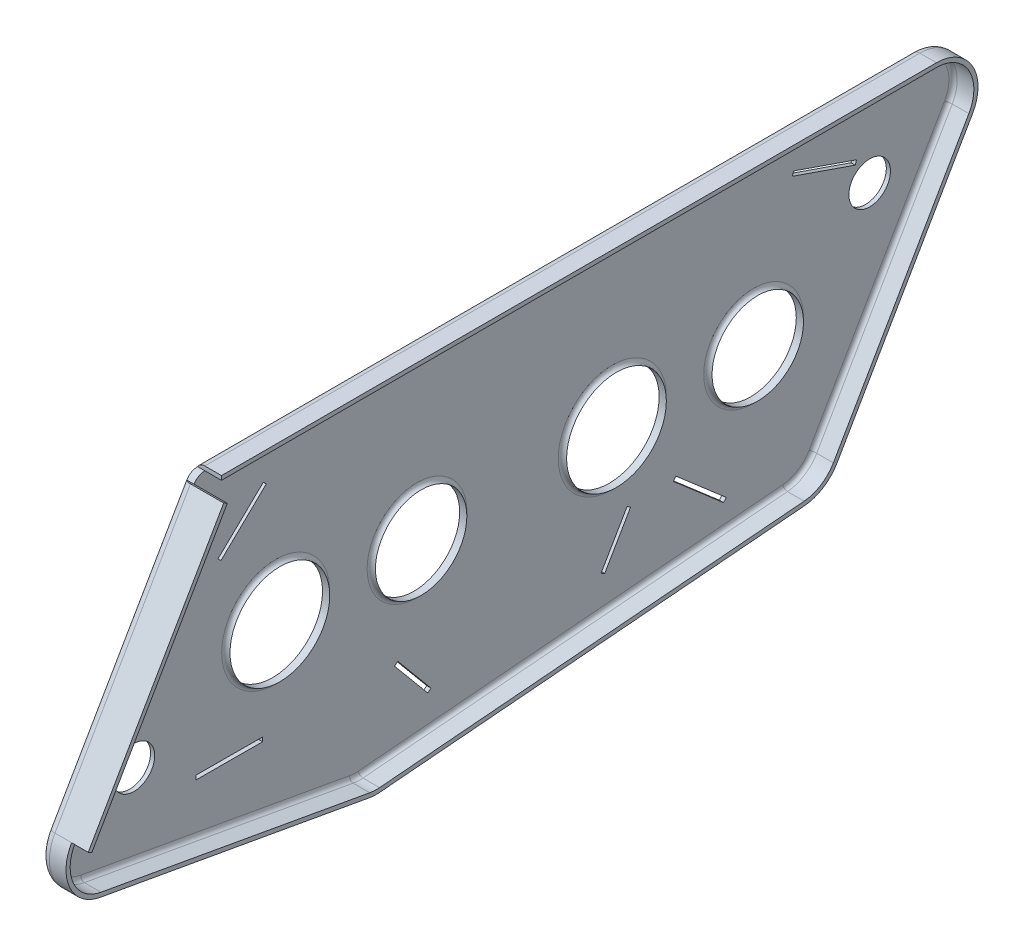
SolidWorks part; units mm, degrees
ref_plane "Front Plane" through (0, 0, 0) normal (0, 0, 1) x (1, 0, 0)
ref_plane "Top Plane" through (0, 0, 0) normal (0, 1, 0) x (1, 0, 0)
ref_plane "Right Plane" through (0, 0, 0) normal (1, 0, 0) x (0, 0, -1)
sketch "Sketch1" plane through (0, 0, 0) normal (1, 0, 0) x (0, 0, -1)
  line L0 (-43.0126, 0) -> (43.0126, 0)
  line L1 (47.3427, -7.5) -> (31.0399, -35.7373)
  line L2 (27.13, -38.2196) -> (-23.95, -42.5276)
  line L3 (-25.2539, -42.4666) -> (-57.6009, -36.6586)
  line L4 (-61.0474, -29.2373) -> (-44.7446, -1)
  arc A0 (-25.2539, -42.4666) -> (-23.95, -42.5276) centre (-24.3702, -37.5453) ccw
  arc A1 (27.13, -38.2196) -> (31.0399, -35.7373) centre (26.7098, -33.2373) ccw
  arc A2 (47.3427, -7.5) -> (43.0126, 0) centre (43.0126, -5) ccw
  arc A3 (-44.7446, -1) -> (-43.0126, 0) centre (-43.0126, -2) cw
  arc A4 (-61.0474, -29.2373) -> (-57.6009, -36.6586) centre (-56.7173, -31.7373) ccw
  point P11 (-24.606, -42.5829)
  point P14 (29.7335, -38)
  point P17 (51.6728, 0)
  point P23 (-64.606, -35.4008)
  dimension "D6" = 5
  dimension "D7" = 5
  dimension "D8" = 83
  dimension "D1" = 2
  dimension "D2" = 120
  dimension "D3" = 40
  dimension "D4" = 38
  dimension "D5" = 165
extrude "Boss-Extrude1" add sketch "Sketch1" along normal mid plane 5
fillet "Fillet2" radius 1 1 edges at (-2.5, -39.5626, 41.4274) type face fillet first side face at (-2.5, -23.3283, 10.6678) second side face at (0, -39.5626, 41.4274)
sketch "Sketch5" plane through (-2.5, 0, 0) normal (-1, 0, 0) x (0, 0, 1)
  line L0 (-43.0126, -1) -> (-23.5126, -1) construction
  line L1 (43.0126, -1) -> (-43.0126, -1) construction
  line L2 (-23.5126, -1) -> (-23.5126, -21) construction
  circle A0 centre (-23.5126, -21) radius 5
  circle A1 centre (-6.5126, -21) radius 5.5
  circle A2 centre (16.9874, -21) radius 5
  circle A3 centre (33.9874, -21) radius 5.5
  circle A4 centre (-37.4767, -11) radius 2
  circle A5 centre (51.0474, -27.6586) radius 2
  dimension "D6" = 11
  dimension "D7" = 10
  dimension "D8" = 10
  dimension "D9" = 11
  dimension "D4" = 13
  dimension "D12" = 4
  dimension "D13" = 10
  dimension "D15" = 4
  dimension "D1" = 19.5
  dimension "D2" = 20
  dimension "D3" = 17
  dimension "D5" = 17
  dimension "D10" = 9
  dimension "D11" = 10
  dimension "D14" = 9
extrude "Cut-Extrude5" cut sketch "Sketch5" against normal through all contours A0 | A1 | A2 | A3 | A5 | A4 region at (-2.5, -21, -23.5126) region at (-2.5, -21, -6.5126) region at (-2.5, -21, 16.9874) region at (-2.5, -21, 33.9874) region at (-2.5, -27.6586, 51.0474)
fillet "Fillet6" radius 1 4 edges at (-2.5, -21, 39.4874) (-2.5, -21, 21.9874) (-2.5, -21, -1.0126) (-2.5, -21, -18.5126)
shell "Shell2" thickness 0.5 removed face at (2.5, -11, -35.4767)
sketch "Sketch6" plane through (2.5, 0, 0) normal (1, 0, 0) x (0, 0, -1)
  circle A0 centre (-33.9874, -21) radius 6 construction
  circle A1 centre (-16.9874, -21) radius 5.5 construction
  circle A2 centre (6.5126, -21) radius 6 construction
  circle A3 centre (23.5126, -21) radius 5.5 construction
  circle A4 centre (-33.9874, -21) radius 6
  circle A5 centre (-16.9874, -21) radius 5.5
  circle A6 centre (6.5126, -21) radius 6
  circle A7 centre (23.5126, -21) radius 5.5
  circle A8 centre (-33.9874, -21) radius 6 construction
  circle A9 centre (-33.9874, -21) radius 5.5 construction
  circle A10 centre (-33.9874, -21) radius 6
  circle A11 centre (-33.9874, -21) radius 5.5
  circle A12 centre (-16.9874, -21) radius 5 construction
  circle A13 centre (6.5126, -21) radius 5.5
  circle A14 centre (6.5126, -21) radius 5.5
  circle A15 centre (-16.9874, -21) radius 5.5 construction
  circle A16 centre (23.5126, -21) radius 5 construction
  circle A17 centre (23.5126, -21) radius 5.5 construction
  circle A18 centre (-16.9874, -21) radius 5
  circle A19 centre (-16.9874, -21) radius 5.5
  circle A20 centre (23.5126, -21) radius 5
  circle A21 centre (23.5126, -21) radius 5.5
  circle A22 centre (6.5126, -21) radius 6 construction
  circle A23 centre (6.5126, -21) radius 5.5 construction
  circle A24 centre (6.5126, -21) radius 6
  circle A25 centre (6.5126, -21) radius 5.5
  dimension "D1" = 0
extrude "Cut-Extrude6" cut sketch "Sketch6" against normal blind 8 contours A5 A18 | A6 A14 | A7 A20 | A11 | A4 region at (2.5, -21, 22.3318) region at (2.5, -21, -0.6823) region at (2.5, -21, -18.1682)
sketch "Sketch9" plane through (2.5, 0, 0) normal (1, 0, 0) x (0, 0, -1)
  circle A0 centre (37.4767, -11) radius 2 construction
  circle A1 centre (-51.0474, -27.6586) radius 2.5
  circle A2 centre (-51.0474, -27.6586) radius 2.5
  circle A3 centre (37.4767, -11) radius 2.5
  circle A4 centre (37.4767, -11) radius 2.5
  circle A5 centre (37.4767, -11) radius 2
  circle M3 centre (-51.0474, -27.6586) radius 2
  circle M4 centre (-51.0474, -27.6586) radius 2.5
  dimension "D1" = 0
  dimension "D2" = 0
extrude "Cut-Extrude8" cut sketch "Sketch9" against normal blind 9 contours M4 M3 | A4 A5 region at (2.5, -27.6586, 53.4767) region at (2.5, -11, -35.0474)
ref_plane "Plane1" through (0, 0, 43.0126) normal (0, 0, 1) x (1, 0, 0)
sketch "Sketch10" plane through (0, -43, 43.0126) normal (0, 0, -1) x (1, 0, 0)
  line L0 (2.5, -43) -> (0.5, -43)
  line L1 (2.5, -43) -> (-1.5, -43) construction
  line L2 (0.5, -43) -> (0.5, -41)
  line L3 (0.5, -41) -> (2.5, -41)
  line L5 (2.5, -41) -> (2.5, -43)
  dimension "D1" = 2
sketch "Sketch11" plane through (2.5, 0, 0) normal (1, 0, 0) x (0, 0, -1)
  line L0 (43.0126, 0) -> (-43.0126, 0) construction
  line L1 (31.0399, -35.7373) -> (47.3427, -7.5) construction
  line L2 (-23.95, -42.5276) -> (27.13, -38.2196) construction
  line L3 (-57.6009, -36.6586) -> (-25.2539, -42.4666) construction
  line L4 (43.0126, 0) -> (-43.0126, 0)
  line L5 (31.0399, -35.7373) -> (47.3427, -7.5)
  line L6 (-23.95, -42.5276) -> (27.13, -38.2196)
  line L7 (-57.6009, -36.6586) -> (-25.2539, -42.4666)
  arc A0 (47.3427, -7.5) -> (43.0126, 0) centre (43.0126, -5) ccw construction
  arc A1 (27.13, -38.2196) -> (31.0399, -35.7373) centre (26.7098, -33.2373) ccw construction
  arc A2 (-25.2539, -42.4666) -> (-23.95, -42.5276) centre (-24.3702, -37.5453) ccw construction
  arc A3 (-61.0474, -29.2373) -> (-57.6009, -36.6586) centre (-56.7173, -31.7373) ccw construction
  arc A4 (47.3427, -7.5) -> (43.0126, 0) centre (43.0126, -5) ccw
  arc A5 (27.13, -38.2196) -> (31.0399, -35.7373) centre (26.7098, -33.2373) ccw
  arc A6 (-25.2539, -42.4666) -> (-23.95, -42.5276) centre (-24.3702, -37.5453) ccw
  arc A7 (-61.0474, -29.2373) -> (-57.6009, -36.6586) centre (-56.7173, -31.7373) ccw
sweep "Cut-Sweep1" cut profiles "Sketch10" path "Sketch11"
sketch "Sketch12" plane through (2.5, 0, 0) normal (1, 0, 0) x (0, 0, -1)
  line L0 (-44.7446, -1) -> (-44.3116, -1.25)
  line L2 (-43.0126, 0) -> (-43.0126, -0.5) construction
  line L3 (-43.0126, 0) -> (-43.0126, -0.5)
  arc A2 (-43.0126, 0) -> (-44.7446, -1) centre (-43.0126, -2) ccw construction
  arc A3 (-43.0126, -0.5) -> (-44.3116, -1.25) centre (-43.0126, -2) ccw construction
  arc A4 (-43.0126, 0) -> (-44.7446, -1) centre (-43.0126, -2) ccw
  arc A5 (-43.0126, -0.5) -> (-44.3116, -1.25) centre (-43.0126, -2) ccw
extrude "Cut-Extrude9" cut sketch "Sketch12" against normal through all
sketch "Sketch16" plane through (-2, 0, 0) normal (1, 0, 0) x (0, 0, -1)
  line L0 (28.3367, -5.1865) -> (35.8957, -7.8062)
  line L1 (35.8957, -7.8062) -> (35.7319, -8.2786)
  line L2 (35.7319, -8.2786) -> (28.173, -5.659)
  line L3 (28.173, -5.659) -> (28.3367, -5.1865)
  line L4 (13.8457, -30.2857) -> (14.173, -29.9077)
  line L5 (14.173, -29.9077) -> (20.2212, -35.1441)
  line L6 (20.2212, -35.1441) -> (19.8939, -35.5221)
  line L7 (19.8939, -35.5221) -> (13.8457, -30.2857)
extrude "Cut-Extrude10" cut sketch "Sketch16" against normal through all
sketch "Sketch17" plane through (-2, 0, 0) normal (1, 0, 0) x (0, 0, -1)
  line L0 (-40.9286, -10.9686) -> (-40.5817, -11.3287)
  line L1 (-40.5817, -11.3287) -> (-35.1248, -6.0722)
  line L2 (-35.1248, -6.0722) -> (-35.4717, -5.7121)
  line L3 (-35.4717, -5.7121) -> (-40.9286, -10.9686)
  line L4 (-43.5647, -32.6844) -> (-43.563, -32.1844)
  line L5 (-43.563, -32.1844) -> (-35.563, -32.212)
  line L6 (-35.563, -32.212) -> (-35.5648, -32.712)
  line L8 (-35.5648, -32.712) -> (-43.5647, -32.6844)
  line L9 (-19.6815, -32.7831) -> (-19.2975, -32.4629)
  line L10 (-19.2975, -32.4629) -> (-15.3148, -37.2395)
  line L11 (-15.3148, -37.2395) -> (-15.6988, -37.5597)
  line L12 (-15.6988, -37.5597) -> (-19.6815, -32.7831)
  line L13 (8.2855, -30.1366) -> (8.7177, -30.3879)
  line L15 (8.7177, -30.3879) -> (5.5913, -35.7641)
  line L16 (5.5913, -35.7641) -> (5.1591, -35.5128)
  line L17 (5.1591, -35.5128) -> (8.2855, -30.1366)
extrude "Cut-Extrude11" cut sketch "Sketch17" against normal through all
